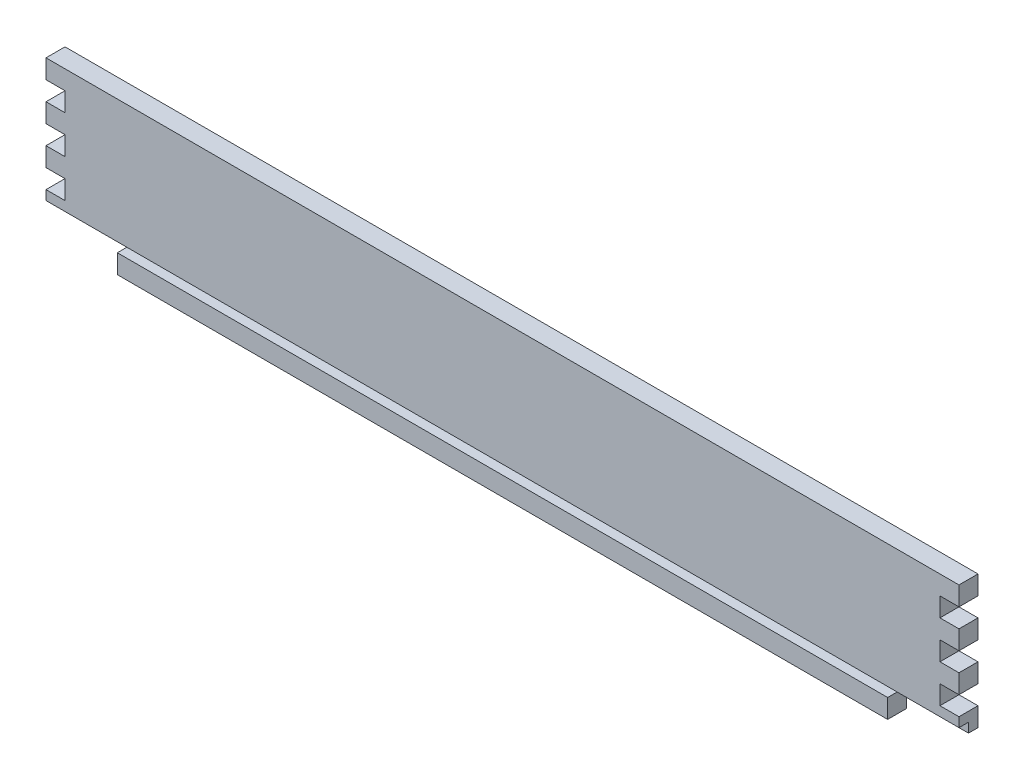
SolidWorks part; units mm, degrees
ref_plane "Front Plane" through (0, 0, 0) normal (0, 0, 1) x (1, 0, 0)
ref_plane "Top Plane" through (0, 0, 0) normal (0, 1, 0) x (1, 0, 0)
ref_plane "Right Plane" through (0, 0, 0) normal (1, 0, 0) x (0, 0, -1)
sketch "Sketch1" plane through (0, 0, 0) normal (0, 0, 1) x (1, 0, 0)
  line L0 (0, 12.7) -> (12.7, 12.7)
  line L1 (12.7, 0) -> (596.9, 0)
  line L2 (0, 12.7) -> (0, 25.4)
  line L3 (0, 101.6) -> (609.6, 101.6)
  line L4 (609.6, 12.7) -> (609.6, 25.4)
  line L5 (12.7, 12.7) -> (12.7, 0)
  line L6 (0, 25.4) -> (12.7, 25.4)
  line L7 (609.6, 12.7) -> (596.9, 12.7)
  line L8 (0, 38.1) -> (12.7, 38.1)
  line L9 (12.7, 38.1) -> (12.7, 25.4)
  line L10 (0, 50.8) -> (12.7, 50.8)
  line L11 (596.9, 12.7) -> (596.9, 0)
  line L12 (0, 63.5) -> (12.7, 63.5)
  line L13 (12.7, 63.5) -> (12.7, 50.8)
  line L14 (0, 76.2) -> (12.7, 76.2)
  line L15 (609.6, 25.4) -> (596.9, 25.4)
  line L16 (0, 88.9) -> (12.7, 88.9)
  line L17 (12.7, 88.9) -> (12.7, 76.2)
  line L18 (0, 101.6) -> (12.7, 101.6)
  line L20 (0, 38.1) -> (0, 50.8)
  line L21 (0, 63.5) -> (0, 76.2)
  line L22 (0, 88.9) -> (0, 101.6)
  line L23 (12.7, 101.6) -> (12.7, 88.9) [skipped]
  line L24 (12.7, 76.2) -> (12.7, 63.5) [skipped]
  line L25 (12.7, 50.8) -> (12.7, 38.1) [skipped]
  line L26 (12.7, 25.4) -> (12.7, 12.7) [skipped]
  line L27 (609.6, 38.1) -> (596.9, 38.1)
  line L28 (596.9, 38.1) -> (596.9, 25.4)
  line L29 (609.6, 50.8) -> (596.9, 50.8)
  line L31 (609.6, 63.5) -> (596.9, 63.5)
  line L32 (596.9, 63.5) -> (596.9, 50.8)
  line L33 (609.6, 76.2) -> (596.9, 76.2)
  line L35 (609.6, 88.9) -> (596.9, 88.9)
  line L36 (596.9, 88.9) -> (596.9, 76.2)
  line L37 (609.6, 101.6) -> (596.9, 101.6)
  line L39 (609.6, 38.1) -> (609.6, 50.8)
  line L40 (609.6, 63.5) -> (609.6, 76.2)
  line L41 (609.6, 88.9) -> (609.6, 101.6)
  line L42 (596.9, 101.6) -> (596.9, 88.9) [skipped]
  line L43 (596.9, 76.2) -> (596.9, 63.5) [skipped]
  line L44 (596.9, 50.8) -> (596.9, 38.1) [skipped]
  line L45 (596.9, 25.4) -> (596.9, 12.7) [skipped]
  dimension "D1" = 101.6
  dimension "D2" = 8
  dimension "D3" = 12.7
  dimension "D4" = 12.7
  dimension "D5" = 12.7
  dimension "D6" = 609.6
  dimension "D7" = 8
extrude "Boss-Extrude1" add sketch "Sketch1" along normal blind 12.7 contours L35 L41 L3 L22 L16 L17 L14 L21 L12 L13 L10 L20 L8 L9 L6 L2 L0 L5 L1 L11 L7 L4 L15 L28 L27 L39 L29 L32 L31 L40 L33 L36 region at (6.35, 19.05, 0) region at (304.8, 50.8, 0) region at (6.35, 44.45, 0) region at (603.25, 19.05, 0) region at (6.35, 69.85, 0) region at (603.25, 44.45, 0) region at (6.35, 95.25, 0) region at (603.25, 69.85, 0) region at (603.25, 95.25, 0)
sketch "Sketch2" plane through (0, 0, 0) normal (0, 0, 1) x (1, 0, 0)
  line L0 (596.9, 12.7) -> (561.975, 12.7)
  line L1 (561.975, 12.7) -> (561.975, 0)
  line L2 (12.7, 0) -> (596.9, 0) construction
  line L3 (12.7, 12.7) -> (47.625, 12.7)
  line L4 (47.625, 12.7) -> (47.625, 0)
  line L5 (596.9, 38.1) -> (596.9, 25.4) construction
  line L6 (12.7, 38.1) -> (12.7, 25.4) construction
  line L7 (596.9, 12.7) -> (596.9, 0)
  line L8 (596.9, 0) -> (561.975, 0)
  line L9 (47.625, 0) -> (12.7, 0)
  line L10 (12.7, 0) -> (12.7, 12.7)
  circle A0 centre (589.7563, 23.8125) radius 3.175
  circle A1 centre (19.8437, 23.8125) radius 3.175
  point P14 (596.9, 31.75)
  dimension "D5" = 6.35
  dimension "D6" = 6.35
  dimension "D1" = 34.925
  dimension "D2" = 34.925
  dimension "D3" = 7.1437
  dimension "D4" = 11.1125
  dimension "D7" = 7.1437
  dimension "D8" = 11.1125
extrude "Cut-Extrude1" cut sketch "Sketch2" along normal through all contours L8 L7 L0 L1 | L10 L9 L4 L3 region at (579.4375, 6.35, 0) region at (30.1625, 6.35, 0)
extrude "Cut-Extrude2" cut sketch "Sketch2<4>" along normal blind 6.35 contours A0 | A1 | A0 region at (589.7563, 23.8125, 0) region at (19.8437, 23.8125, 0)
sketch "Sketch2<4>" plane through (0, 0, 0) normal (0, 0, 1) x (1, 0, 0) same geometry as "Sketch2"
sketch "Sketch3" plane through (0, 0, 12.7) normal (0, 0, 1) x (1, 0, 0)
  line L0 (47.625, 0) -> (561.975, 0) construction
  line L1 (-14.7942, 19.05) -> (665.121, 19.05)
  line L2 (-14.7942, 19.05) -> (-14.7942, 12.7)
  line L3 (-14.7942, 12.7) -> (665.121, 12.7)
  line L4 (665.121, 19.05) -> (665.121, 12.7)
  dimension "D1" = 6.35
  dimension "D2" = 12.7
extrude "Cut-Extrude3" cut sketch "Sketch3" against normal blind 6.35
